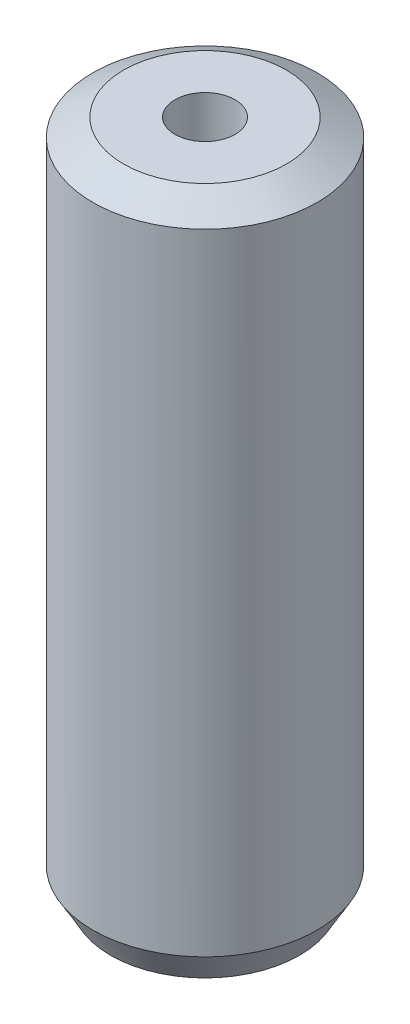
SolidWorks part; units mm, degrees
ref_plane "Front Plane" through (0, 0, 0) normal (0, 0, 1) x (1, 0, 0)
ref_plane "Top Plane" through (0, 0, 0) normal (0, 1, 0) x (1, 0, 0)
ref_plane "Right Plane" through (0, 0, 0) normal (1, 0, 0) x (0, 0, -1)
sketch "Sketch1" plane through (0, 0, 0) normal (0, 1, 0) x (1, 0, 0)
  circle A0 centre (0, 0) radius 5
  dimension "SHAFT_OD" = 10
extrude "Boss-Extrude1" add sketch "Sketch1" along normal blind 30.2308
sketch "Sketch2" plane through (0, 0, 0) normal (0, 1, 0) x (1, 0, 0)
  circle A0 centre (0, 0) radius 1.3386
  dimension "BORE_D" = 2.6772
extrude "Cut-Extrude1" cut sketch "Sketch2" along normal through all
chamfer "Chamfer1" distance 0.7923 angle 60 2 edges at (0, 30.2308, 5) (0, 0, 5) first distance on face at (0, 30.2308, 5) first distance on face at (0, 0, 1.3386)
